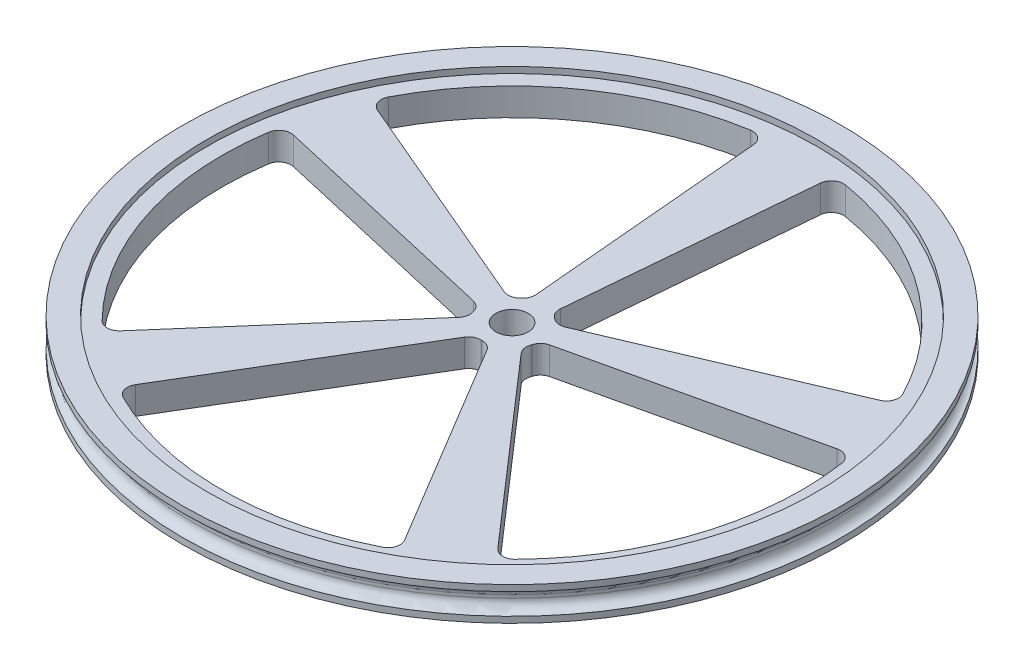
SolidWorks part; units mm, degrees
ref_plane "前视基准面" through (0, 0, 0) normal (0, 0, 1) x (1, 0, 0)
ref_plane "上视基准面" through (0, 0, 0) normal (0, 1, 0) x (1, 0, 0)
ref_plane "右视基准面" through (0, 0, 0) normal (1, 0, 0) x (0, 0, -1)
sketch "草图1" [suppressed] plane through (0, 0, 0) normal (0, 1, 0) x (1, 0, 0)
  line L0 (1.9045, 4.6231) -> (3.2705, 20.2374)
  line L1 (0, 0) -> (-46.3157, 15.0489) construction
  line L2 (-4.9853, -0.3826) -> (-20.2576, 3.1432)
  line L3 (-0.4635, -1.4266) -> (-46.7792, 13.6223) construction
  line L4 (0, 0) -> (0, 48.6992) construction
  line L5 (-4.9994, 3.7455) -> (-16.1389, 8.4739)
  line L6 (-1.5, 0) -> (-1.5, 48.6992) construction
  line L7 (-1.5, 0) -> (-1.5439, 0.5016)
  line L8 (-2.0172, 5.9122) -> (-3.072, 17.9676)
  circle A0 centre (0, 0) radius 25.5
  arc A1 (-4.9853, -0.3826) -> (0, 5) centre (0, 0) ccw
  arc A2 (-20.2576, 3.1432) -> (3.2705, 20.2374) centre (0, 0) ccw
  arc A3 (-5.6119, 19.7169) -> (-17.0178, 11.4301) centre (0, 0) ccw
  arc A4 (-2.864, 4.0985) -> (-3.0128, 3.9903) centre (0, 0) ccw
  arc A5 (-3.072, 17.9676) -> (-5.6119, 19.7169) centre (-5.0644, 17.7933) ccw
  arc A6 (-16.1389, 8.4739) -> (-17.0178, 11.4301) centre (-15.3575, 10.3149) cw
  arc A7 (-3.0128, 3.9903) -> (-4.9994, 3.7455) centre (-4.218, 5.5865) cw
  arc A8 (-2.0172, 5.9122) -> (-2.864, 4.0985) centre (-4.0096, 5.7378) cw
  point P19 (0, 0)
  point P24 (-18.2363, 9.3642)
  point P29 (-1.9045, 4.6231)
  dimension "D3" = 51
  dimension "D4" = 5
  dimension "D5" = 10
  dimension "D7" = 2
  dimension "D8" = 2
  dimension "D9" = 2
  dimension "D1" = 2
  dimension "D2" = 5
  dimension "D6" = 1.5
sketch "草图2" plane through (0, 0, 0) normal (0, 1, 0) x (1, 0, 0)
  line L0 (-5.1048, -3.6085) -> (-30.9085, -33.2414)
  line L1 (0, 0) -> (-46.3157, 15.0489) construction
  line L2 (-4.7553, -1.5451) -> (-45.1752, -14.6783) construction
  line L3 (-0.4635, -1.4266) -> (-46.7792, 13.6223) construction
  line L4 (0, 0) -> (0, 48.6992) construction
  line L5 (-5.0093, 3.7398) -> (-41.1657, 19.1236)
  line L6 (-1.5, 0) -> (-1.5, 48.6992) construction
  line L7 (-6.2508, -0.0812) -> (-44.5443, 8.7253)
  line L8 (-2.0088, 5.9198) -> (-5.4667, 45.0605)
  line L10 (1.8946, 4.6271) -> (3.274, 20.2403) [skipped]
  line L11 (1.8544, -5.97) -> (22.0632, -39.6679)
  line L12 (-1.8544, -5.97) -> (-22.0632, -39.6679)
  line L13 (6.2508, -0.0812) -> (44.5443, 8.7253)
  line L14 (5.1048, -3.6085) -> (30.9085, -33.2414)
  line L15 (2.0088, 5.9198) -> (5.4667, 45.0605)
  line L16 (5.0093, 3.7398) -> (41.1657, 19.1236)
  circle A0 centre (0, 0) radius 52.5
  arc A1 (-30.9085, -33.2414) -> (-33.8418, -33.3315) centre (-32.4168, -31.928) cw
  arc A2 (-46.9703, 7.074) -> (-33.8418, -33.3315) centre (0, 0) ccw
  arc A3 (-7.7868, 46.8574) -> (-42.1578, 21.8854) centre (0, 0) ccw
  arc A4 (-2.8579, 4.1027) -> (-3.0188, 3.9858) centre (0, 0) ccw
  arc A5 (-5.4667, 45.0605) -> (-7.7868, 46.8574) centre (-7.459, 44.8845) ccw
  arc A6 (-41.1657, 19.1236) -> (-42.1578, 21.8854) centre (-40.3827, 20.9639) cw
  arc A7 (-3.0188, 3.9858) -> (-5.0093, 3.7398) centre (-4.2263, 5.5802) cw
  arc A8 (-2.0088, 5.9198) -> (-2.8579, 4.1027) centre (-4.0011, 5.7438) cw
  arc A9 (-44.5443, 8.7253) -> (-46.9703, 7.074) centre (-44.9926, 6.7762) ccw
  arc A10 (-6.2508, -0.0812) -> (-4.7851, -1.4502) centre (-6.6991, -2.0303) cw
  arc A11 (-4.7236, -1.6393) -> (-5.1048, -3.6085) centre (-6.6131, -2.2951) cw
  arc A12 (-4.7851, -1.4502) -> (-4.7236, -1.6393) centre (0, 0) ccw
  arc A13 (22.0632, -39.6679) -> (21.2424, -42.4854) centre (20.348, -40.6965) cw
  arc A14 (-21.2424, -42.4854) -> (21.2424, -42.4854) centre (0, 0) ccw
  arc A15 (-22.0632, -39.6679) -> (-21.2424, -42.4854) centre (-20.348, -40.6965) ccw
  arc A16 (-1.8544, -5.97) -> (-0.0994, -4.999) centre (-0.1392, -6.9986) cw
  arc A17 (0.0994, -4.999) -> (1.8544, -5.97) centre (0.1392, -6.9986) cw
  arc A18 (-0.0994, -4.999) -> (0.0994, -4.999) centre (0, 0) ccw
  arc A19 (44.5443, 8.7253) -> (46.9703, 7.074) centre (44.9926, 6.7762) cw
  arc A20 (33.8418, -33.3315) -> (46.9703, 7.074) centre (0, 0) ccw
  arc A21 (30.9085, -33.2414) -> (33.8418, -33.3315) centre (32.4168, -31.928) ccw
  arc A22 (5.1048, -3.6085) -> (4.7236, -1.6393) centre (6.6131, -2.2951) cw
  arc A23 (4.7851, -1.4502) -> (6.2508, -0.0812) centre (6.6991, -2.0303) cw
  arc A24 (4.7236, -1.6393) -> (4.7851, -1.4502) centre (0, 0) ccw
  arc A25 (5.4667, 45.0605) -> (7.7868, 46.8574) centre (7.459, 44.8845) cw
  arc A26 (42.1578, 21.8854) -> (7.7868, 46.8574) centre (0, 0) ccw
  arc A27 (41.1657, 19.1236) -> (42.1578, 21.8854) centre (40.3827, 20.9639) ccw
  arc A28 (5.0093, 3.7398) -> (3.0188, 3.9858) centre (4.2263, 5.5802) cw
  arc A29 (2.8579, 4.1027) -> (2.0088, 5.9198) centre (4.0011, 5.7438) cw
  arc A30 (3.0188, 3.9858) -> (2.8579, 4.1027) centre (0, 0) ccw
  circle A31 centre (0, 0) radius 2.65
  circle A32 centre (0, 0) radius 6.2514 construction
  point P19 (0, 0)
  point P24 (-43.1075, 19.9498)
  point P29 (-1.8946, 4.6271)
  point P81 (0, 0)
  dimension "D3" = 105
  dimension "D4" = 5
  dimension "D5" = 5.3
  dimension "D7" = 0.5088
  dimension "D8" = 5.049
  dimension "D9" = 12.5028
  dimension "D10" = 2
  dimension "D11" = 5
  dimension "D12" = 36
  dimension "D13" = 5
  dimension "D1" = 2
  dimension "D2" = 72
  dimension "D6" = 1.5
extrude "凸台-拉伸1" add sketch "草图2" along normal mid plane 5.5
sketch "草图3" plane through (0, 2.75, 0) normal (0, 1, 0) x (1, 0, 0)
  circle A0 centre (0, 0) radius 54
  circle A1 centre (0, 0) radius 52.5 construction
  circle A2 centre (0, 0) radius 52.5
  dimension "D1" = 1.5
extrude "凸台-拉伸2" add sketch "草图3" against normal blind 1
sketch "草图4" plane through (0, 2.75, 0) normal (0, 1, 0) x (1, 0, 0)
  circle A0 centre (0, 0) radius 50
  arc A1 (-7.7868, 46.8574) -> (-42.1578, 21.8854) centre (0, 0) ccw construction
  arc A2 (-7.7868, 46.8574) -> (-42.1578, 21.8854) centre (0, 0) ccw
  arc M2 (-6.2508, -0.0812) -> (-4.7851, -1.4502) centre (-6.6991, -2.0303) cw
  arc M3 (-4.7851, -1.4502) -> (-4.7236, -1.6393) centre (0, 0) ccw
  arc M4 (-4.7236, -1.6393) -> (-5.1048, -3.6085) centre (-6.6131, -2.2951) cw
  line M5 (-5.1048, -3.6085) -> (-30.9085, -33.2414)
  arc M6 (-30.9085, -33.2414) -> (-33.8418, -33.3315) centre (-32.4168, -31.928) cw
  arc M7 (-33.8418, -33.3315) -> (-46.9703, 7.074) centre (0, 0) cw
  arc M8 (-46.9703, 7.074) -> (-44.5443, 8.7253) centre (-44.9926, 6.7762) cw
  circle M9 centre (0, 0) radius 2.65
  line M10 (-5.4667, 45.0605) -> (-2.0088, 5.9198)
  arc M11 (-2.0088, 5.9198) -> (-2.8579, 4.1027) centre (-4.0011, 5.7438) cw
  arc M12 (-2.8579, 4.1027) -> (-3.0188, 3.9858) centre (0, 0) ccw
  arc M13 (-3.0188, 3.9858) -> (-5.0093, 3.7398) centre (-4.2263, 5.5802) cw
  line M14 (-5.0093, 3.7398) -> (-41.1657, 19.1236)
  arc M15 (-41.1657, 19.1236) -> (-42.1578, 21.8854) centre (-40.3827, 20.9639) cw
  arc M16 (-42.1578, 21.8854) -> (-7.7868, 46.8574) centre (0, 0) cw
  arc M17 (-7.7868, 46.8574) -> (-5.4667, 45.0605) centre (-7.459, 44.8845) cw
  arc M18 (-1.8544, -5.97) -> (-0.0994, -4.999) centre (-0.1392, -6.9986) cw
  arc M19 (-0.0994, -4.999) -> (0.0994, -4.999) centre (0, 0) ccw
  arc M20 (0.0994, -4.999) -> (1.8544, -5.97) centre (0.1392, -6.9986) cw
  line M21 (1.8544, -5.97) -> (22.0632, -39.6679)
  arc M22 (22.0632, -39.6679) -> (21.2424, -42.4854) centre (20.348, -40.6965) cw
  arc M23 (21.2424, -42.4854) -> (-21.2424, -42.4854) centre (0, 0) cw
  arc M24 (-21.2424, -42.4854) -> (-22.0632, -39.6679) centre (-20.348, -40.6965) cw
  line M25 (-22.0632, -39.6679) -> (-1.8544, -5.97)
  arc M26 (5.1048, -3.6085) -> (4.7236, -1.6393) centre (6.6131, -2.2951) cw
  arc M27 (4.7236, -1.6393) -> (4.7851, -1.4502) centre (0, 0) ccw
  arc M28 (4.7851, -1.4502) -> (6.2508, -0.0812) centre (6.6991, -2.0303) cw
  line M29 (6.2508, -0.0812) -> (44.5443, 8.7253)
  arc M30 (44.5443, 8.7253) -> (46.9703, 7.074) centre (44.9926, 6.7762) cw
  arc M31 (46.9703, 7.074) -> (33.8418, -33.3315) centre (0, 0) cw
  arc M32 (33.8418, -33.3315) -> (30.9085, -33.2414) centre (32.4168, -31.928) cw
  line M33 (30.9085, -33.2414) -> (5.1048, -3.6085)
  arc M34 (5.0093, 3.7398) -> (3.0188, 3.9858) centre (4.2263, 5.5802) cw
  arc M35 (3.0188, 3.9858) -> (2.8579, 4.1027) centre (0, 0) ccw
  arc M36 (2.8579, 4.1027) -> (2.0088, 5.9198) centre (4.0011, 5.7438) cw
  line M37 (2.0088, 5.9198) -> (5.4667, 45.0605)
  arc M38 (5.4667, 45.0605) -> (7.7868, 46.8574) centre (7.459, 44.8845) cw
  arc M39 (7.7868, 46.8574) -> (42.1578, 21.8854) centre (0, 0) cw
  arc M40 (42.1578, 21.8854) -> (41.1657, 19.1236) centre (40.3827, 20.9639) cw
  line M41 (41.1657, 19.1236) -> (5.0093, 3.7398)
  line M44 (-44.5443, 8.7253) -> (-6.2508, -0.0812)
  dimension "D1" = 2.5
extrude "切除-拉伸1" cut sketch "草图4" against normal blind 1 contours A0 M9 M41 M34 M35 M36 M37 M38 M39 M40 M33 M26 M27 M28 M29 M30 M31 M32 M25 M18 M19 M20 M21 M22 M23 M24 M44 M2 M3 M4 M5 M6 M7 M8 M17 M10 M11 M12 M13 M14 M15 M16
mirror "镜向1" about plane through (0, 0, 0) normal (0, 1, 0) of "凸台-拉伸2"
fillet "圆角1" radius 1.5 2 edges at (0, 1.75, 52.5) (0, -1.75, -52.5)
